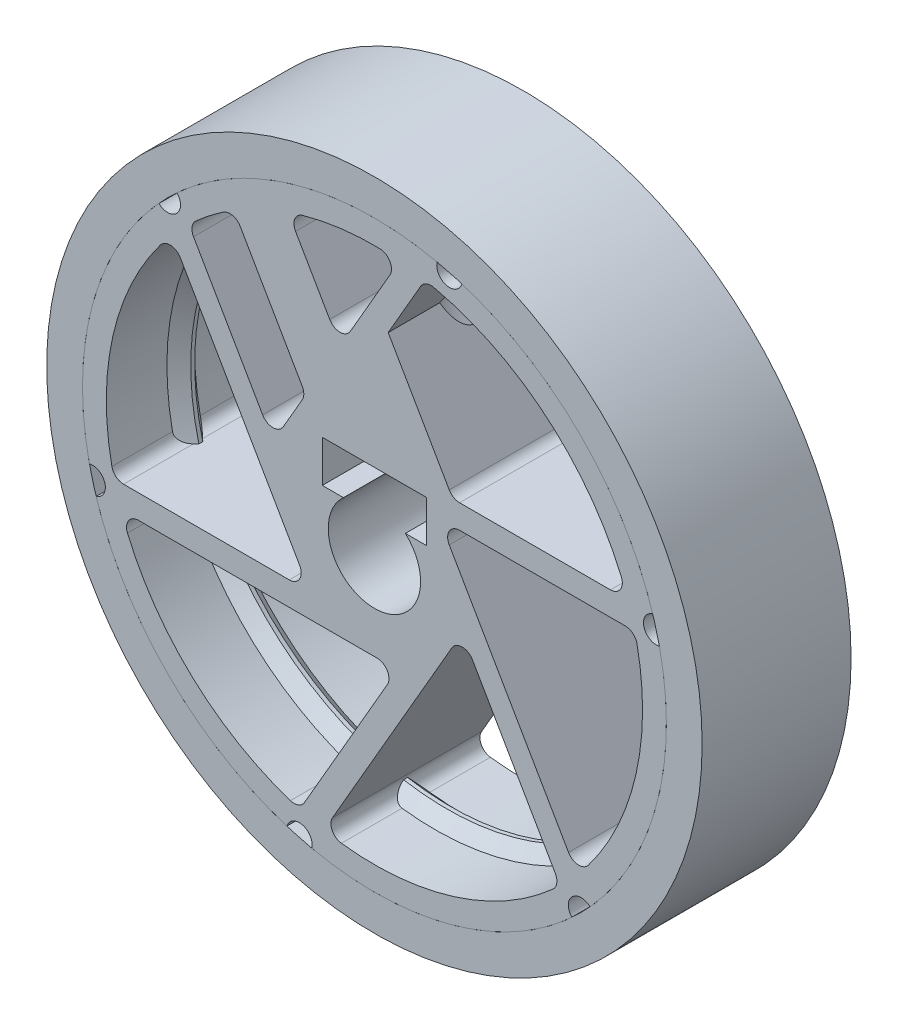
SolidWorks part; units mm, degrees
other "tire-mock"
other "hub"
ref_plane "Front Plane" through (0, 0, 0) normal (0, 0, 1) x (1, 0, 0)
ref_plane "Top Plane" through (0, 0, 0) normal (0, 1, 0) x (1, 0, 0)
ref_plane "Right Plane" through (0, 0, 0) normal (1, 0, 0) x (0, 0, -1)
sketch "Sketch1" plane through (0, 0, 0) normal (0, 0, 1) x (1, 0, 0)
  line L0 (2.0785, 2.3) -> (3.5, 2.3)
  line L1 (3.5, 2.3) -> (3.5, 5.1)
  line L2 (3.5, 5.1) -> (-3.5, 5.1)
  line L3 (-3.5, 5.1) -> (-3.5, 2.3)
  line L4 (-3.5, 2.3) -> (-2.0785, 2.3)
  line L5 (-1.9261, 2.3) -> (1.9261, 2.3) construction
  line L6 (-6.8127, 0) -> (-13.6123, 11.7773)
  line L7 (3.4064, -5.9) -> (6.8127, 0) construction
  line L8 (6.8127, 0) -> (3.4064, 5.9) construction
  line L9 (3.4064, 5.9) -> (-3.4064, 5.9) construction
  line L10 (-3.4064, 5.9) -> (-6.8127, 0) construction
  line L11 (-6.8127, 0) -> (-3.4064, -5.9) construction
  line L12 (-3.4064, -5.9) -> (3.4064, -5.9) construction
  line L13 (-3.4064, -5.9) -> (-17.0056, -5.9)
  line L14 (3.4064, -5.9) -> (-3.3932, -17.6773)
  line L15 (6.8127, 0) -> (13.6123, -11.7773)
  line L16 (-5.889, 1.6) -> (-12.4633, 12.9871) construction
  line L17 (5.889, -1.6) -> (12.4633, -12.9871)
  line L18 (1.5588, -5.9) -> (-5.0155, -17.2871)
  line L19 (-4.3301, -4.3) -> (-17.4788, -4.3)
  line L20 (3.4064, 5.9) -> (17.0056, 5.9) construction
  line L21 (4.3301, 4.3) -> (17.4788, 4.3)
  line L22 (-12.4633, 12.9871) -> (-6.8127, 3.2)
  line L23 (-6.8127, 3.2) -> (-3.3459, 9.2048)
  line L24 (-3.3459, 9.2048) -> (3.3459, 9.2048) construction
  line L25 (3.3459, 9.2048) -> (5.2539, 5.9)
  line L26 (5.2539, 5.9) -> (17.0056, 5.9)
  line L29 (-6.8127, 0) -> (-4.3301, -4.3)
  line L30 (-3.4064, -5.9) -> (1.5588, -5.9)
  line L31 (3.4064, -5.9) -> (5.889, -1.6)
  line L32 (6.8127, 0) -> (4.3301, 4.3)
  line L33 (-3.3459, 9.2048) -> (1.6863, 17.9208)
  line L34 (3.3932, 17.6773) -> (-1.4983, 9.2048)
  line L35 (3.3459, 9.2048) -> (-1.4983, 9.2048)
  line L36 (11.1297, 5.9) -> (11.1297, 4.3) construction
  line L37 (-0.8298, 13.5628) -> (0.5559, 12.7628) construction
  circle A0 centre (0, 0) radius 3 construction
  circle A1 centre (0, 0) radius 3.1 construction
  arc A2 (-2.0785, 2.3) -> (2.0785, 2.3) centre (0, 0) ccw
  circle A3 centre (0, 0) radius 5.9 construction
  circle A4 centre (0, 0) radius 22 construction
  circle A6 centre (0, 0) radius 19.6
  circle A7 centre (0, 0) radius 18 construction
  arc A8 (1.6863, 17.9208) -> (-12.4633, 12.9871) centre (0, 0) ccw
  arc A9 (-13.6123, 11.7773) -> (-17.4788, -4.3) centre (0, 0) ccw
  arc A10 (-5.0155, -17.2871) -> (-17.0056, -5.9) centre (0, 0) cw
  arc A11 (12.4633, -12.9871) -> (-3.3932, -17.6773) centre (0, 0) cw
  arc A12 (17.4788, 4.3) -> (13.6123, -11.7773) centre (0, 0) cw
  arc A13 (17.0056, 5.9) -> (3.3932, 17.6773) centre (0, 0) ccw
  point P13 (0, -3)
  point P43 (0, 9.2048)
  point P55 (-19.6, 0)
  point P56 (19.6, 0)
  point P58 (0, -19.6)
  point P59 (0, 19.6)
  point P61 (-18, 0)
  point P65 (0, 0)
  point P66 (0, 0)
  point P67 (0, 0)
  dimension "D1" = 6
  dimension "D7" = 44
  dimension "D3" = 7
  dimension "D4" = 2.8
  dimension "D5" = 5.3
  dimension "D6" = 0.8
  dimension "D10" = 1.6
  dimension "D11" = 4.1048
  dimension "D12" = 1.6
  dimension "D2" = 0.1
  dimension "D8" = 2.4
  dimension "D9" = 1.6
extrude "Boss-Extrude1" add sketch "Sketch1" along normal blind 10
ref_axis "Axis1" through (0, 0, 10) along (0, 0, -1)
sketch "Sketch9" plane through (0, 0, 0) normal (0, 0, -1) x (-1, 0, 0)
  line L0 (-3.3459, 9.2048) -> (-0.9238, 13.4)
  line L1 (-3.3459, 9.2048) -> (-5.2539, 5.9) construction
  line L2 (-3.3932, 17.6773) -> (1.4983, 9.2048) construction
  line L3 (-0.9238, 13.4) -> (1.4983, 9.2048)
  line L4 (1.4983, 9.2048) -> (-3.3459, 9.2048)
extrude "Boss-Extrude3" add sketch "Sketch9" against normal up to surface (10 mm away) up to face at (19.6, 0, 10)
sketch "Sketch10" plane through (0, 0, 0) normal (0, 0, -1) x (-1, 0, 0)
  line L0 (2.3094, 11) -> (6.6114, 18.4513)
  line L1 (3.3459, 9.2048) -> (-1.6863, 17.9208) construction
  line L2 (6.6114, 18.4513) -> (10.2298, 16.7186)
  line L3 (10.2298, 16.7186) -> (4.6188, 7)
  line L4 (4.6188, 7) -> (2.3094, 11)
  line L5 (-3.3459, 9.2048) -> (-5.2539, 5.9) construction
  circle A0 centre (0, 0) radius 19.6 construction
  point P4 (0, 0)
  point P9 (0, 0)
  dimension "D1" = 4
  dimension "D2" = 4
extrude "Boss-Extrude6" add sketch "Sketch10" against normal up to surface (10 mm away) up to face at (7.0386, 11.1752, 10)
fillet "Fillet1" radius 0.8 8 edges at (4.3301, 4.3, 5) (5.889, -1.6, 5) (1.5588, -5.9, 5) (-4.3301, -4.3, 5) (-6.8127, 3.2, 5) (5.2539, 5.9, 5) (-4.6188, 7, 5) (-2.3094, 11, 5)
fillet "Fillet2" radius 0.8 8 edges at (13.6123, -11.7773, 5) (17.0056, 5.9, 5) (-13.6123, 11.7773, 5) (-17.0056, -5.9, 5) (-3.3932, -17.6773, 5) (1.6863, 17.9208, 5) (-9.4295, 15.3324, 5) (-5.7971, 17.0409, 5)
fillet "Fillet3" radius 0.8 6 edges at (-17.4788, -4.3, 5) (-12.4633, 12.9871, 5) (17.4788, 4.3, 5) (12.4633, -12.9871, 5) (-5.0155, -17.2871, 5) (3.3932, 17.6773, 5)
sketch "Sketch8" [suppressed] plane through (0, 0, 10) normal (0, 0, 1) x (1, 0, 0)
  line L1 (-3.4613, 18.0715) -> (3.4613, 18.0715)
  line L2 (-3.4613, 18.0715) -> (-3.4613, 9.4048)
  line L3 (-3.4613, 9.4048) -> (3.4613, 9.4048)
  line L4 (3.4613, 18.0715) -> (3.4613, 9.4048)
  line L5 (0, 9.4048) -> (0, 18.0715) construction
  line L6 (-3.4613, 13.7382) -> (3.4613, 13.7382) construction
  circle A0 centre (0, 0) radius 18.4 construction
  point P0 (0, 13.7382)
  point P4 (0, 0)
  point P5 (0, 0)
  point P8 (0, 0)
extrude "Boss-Extrude2" [suppressed] add sketch "Sketch8" against normal up to surface (10 mm away) up to face at (-8.3312, 9.7549, 0)
sketch "Sketch2" plane through (0, 5.1, 0) normal (0, -1, 0) x (1, 0, 0)
  line L0 (0, 10) -> (0, 0) construction
  line L1 (3.5, 10) -> (-3.5, 10) construction
  line L2 (3.5, 0) -> (-3.5, 0) construction
  circle A0 centre (0, 5) radius 1.8
  dimension "D1" = 3.6
extrude "Cut-Extrude1" cut sketch "Sketch2" against normal up to surface (12.8098 mm away) up to face at (10.9125, 13.0451, 5)
sketch "Sketch5" plane through (0, 0, 0) normal (0, 1, 0) x (1, 0, 0)
  line L0 (-19.6, -3.6) -> (-19.6, -6.4)
  line L3 (-19.6, -3.6) -> (-18.8, -4.4)
  line L4 (-18.8, -4.4) -> (-18.8, -5.6)
  line L5 (-18.8, -5.6) -> (-19.6, -6.4)
  point P3 (-19.6, -5)
  dimension "D1" = 0.8
  dimension "D2" = 45
  dimension "D3" = 1.2
sketch "Sketch7" plane through (0, 0, 0) normal (0, 1, 0) x (1, 0, 0)
  line L0 (-19.6, -2.4686) -> (-19.6, -7.5314)
  line L1 (-19.6, -7.5314) -> (-17.2, -5.1314)
  line L2 (-17.2, -5.1314) -> (-17.2, -4.8686)
  line L3 (-17.2, -4.8686) -> (-19.6, -2.4686)
  line L4 (-18.8, -5.6) -> (-19.6, -6.4) construction
  line L5 (-19.6, -3.6) -> (-19.6, -6.4) construction
  line L6 (-18.8, -4.4) -> (-18.8, -5.6) construction
  point P6 (-19.6, -5)
  dimension "D1" = 1.6
  dimension "D2" = 0.8
revolve "Revolve1" add sketch "Sketch7" angle 360 about axis through (0, 0, 10) along (0, 0, -1)
sketch "Sketch6" plane through (0, 5.1, 0) normal (0, -1, 0) x (1, 0, 0)
  circle A0 centre (0, 5) radius 1.4
  dimension "D1" = 2.8
extrude "Cut-Extrude3" cut sketch "Sketch6" against normal through all
sketch "Sketch3" plane through (0, 0, 10) normal (0, 0, 1) x (1, 0, 0)
  line L0 (2.4826, -5.9) -> (-5.0457, -18.9394) construction
  line L1 (-3.4064, -5.9) -> (3.4064, -5.9) construction
  line L2 (1.5588, -5.9) -> (-5.0155, -17.2871) construction
  line L3 (1.5588, -5.9) -> (3.4064, -5.9) construction
  circle A0 centre (-5.0457, -18.9394) radius 0.8625
  circle A1 centre (0, 0) radius 19.6 construction
  circle A2 centre (0, 0) radius 18 construction
  circle A3 centre (-18.9249, -5.1) radius 0.8625
  circle A4 centre (-13.8792, 13.8394) radius 0.8625
  circle A5 centre (5.0457, 18.9394) radius 0.8625
  circle A6 centre (18.9249, 5.1) radius 0.8625
  circle A7 centre (13.8792, -13.8394) radius 0.8625
  point P14 (2.4826, -5.9)
  point P15 (-4.6145, -18.1925)
  point P16 (-4.2145, -17.4997)
  point P32 (0, 0)
  dimension "D1" = 0.8
  dimension "D2" = 6
extrude "Cut-Extrude2" cut sketch "Sketch3" against normal through all
revolve "Cut-Revolve2" cut sketch "Sketch5" angle 360 about axis through (0, 0, 10) along (0, 0, -1)
sketch "Sketch11" plane through (0, 0, 10) normal (0, 0, 1) x (1, 0, 0)
  circle A0 centre (0, 0) radius 22 construction
  circle A1 centre (0, 0) radius 22
  circle A2 centre (0, 0) radius 19.6 construction
  circle A3 centre (0, 0) radius 19.6
extrude "Boss-Extrude7" add sketch "Sketch11" against normal up to surface (10 mm away) separate body up to face at (-8.3312, 9.7549, 0)
